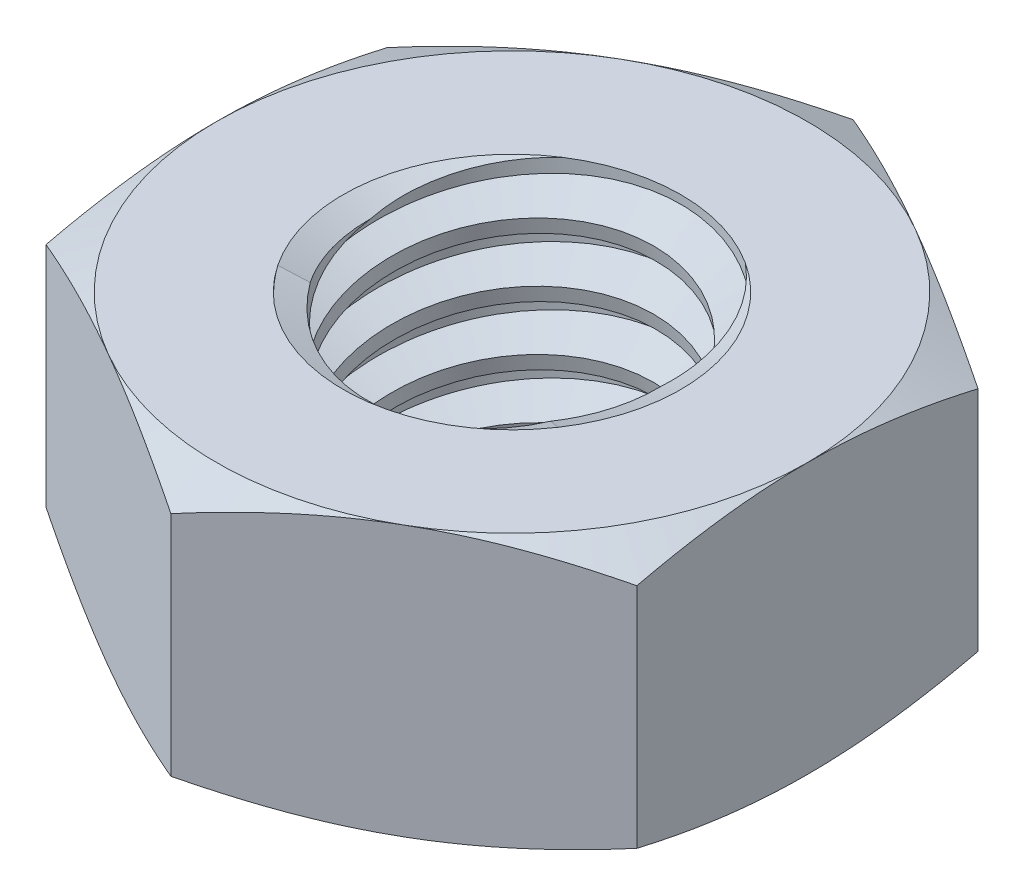
SolidWorks part; units mm, degrees
ref_plane "Front" through (0, 0, 0) normal (0, 0, 1) x (1, 0, 0)
ref_plane "Top" through (0, 0, 0) normal (0, 1, 0) x (1, 0, 0)
ref_plane "Right" through (0, 0, 0) normal (1, 0, 0) x (0, 0, -1)
sketch "Sketch1" plane through (0, 0, 0) normal (0, 1, 0) x (1, 0, 0)
  line L1 (0, 4.0415) -> (-3.5, 2.0207)
  line L2 (-3.5, 2.0207) -> (-3.5, -2.0207)
  line L3 (-3.5, -2.0207) -> (0, -4.0415)
  line L4 (0, -4.0415) -> (3.5, -2.0207)
  line L5 (3.5, -2.0207) -> (3.5, 2.0207)
  line L6 (3.5, 2.0207) -> (0, 4.0415)
  circle A0 centre (0, 0) radius 3.5 construction
  dimension "Hex Flats" = 7
extrude "Extrude1" add sketch "Sketch1" along normal mid plane 3.2
sketch "Sketch2" plane through (0, 0, 0) normal (1, 0, 0) x (0, 0, -1)
  line L0 (-2, -1.6) -> (-2, 1.6) construction
  line L1 (0, -1.6) -> (2, -1.6)
  line L2 (0, -1.6) -> (0, 1.6)
  line L3 (0, 1.6) -> (2, 1.6)
  line L4 (2, -1.6) -> (2, 1.6)
  line L5 (-2.0207, 1.6) -> (2.0207, 1.6) construction
  line L6 (-2.0207, -1.6) -> (2.0207, -1.6) construction
  line L7 (0, -3.6) -> (0, -1.6) construction
  dimension "Thread Dia" = 4
revolve "Revolve1" add sketch "Sketch2" angle 360 about L7
sketch "Sketch3" plane through (0, 0, 0) normal (1, 0, 0) x (0, 0, -1)
  line L0 (2, 1.6) -> (-2, 1.6) construction
  line L1 (-2, 1.6) -> (-2, 0.9) construction
  line L2 (-2, 0.9) -> (2, 1.6) construction
  line L3 (2, 1.6) -> (2.0151, 1.5138) construction
  line L4 (2.0151, 1.5138) -> (2.1207, 0.9105)
  line L5 (2.1207, 0.9105) -> (1.7097, 1.0606)
  line L6 (1.7097, 1.0606) -> (1.6796, 1.233)
  line L7 (1.6796, 1.233) -> (2.0151, 1.5138)
  line L8 (1.6947, 1.1468) -> (2.0679, 1.2121) construction
  line L9 (2, 1.6) -> (2, 1.2003) construction
  line L10 (2, 1.2003) -> (-2, 0.5003) construction
  line L11 (-2, 0.5003) -> (-2, 0.9) construction
  line L12 (-0.1312, 1.6) -> (0.1312, 0.1005) construction
  line L13 (-2, -1.6) -> (-2, 1.6) construction
  line L14 (0, 1.6) -> (2, 1.6) construction
  line L15 (2, -1.6) -> (2, 1.6) construction
  line L16 (0, 0) -> (0, 1.6) construction
  line L17 (-2.0151, 1.5138) -> (-2.1207, 0.9105) construction
  line L18 (-1.6796, 1.233) -> (-2.0151, 1.5138) construction
  line L19 (-1.7097, 1.0606) -> (-1.6796, 1.233) construction
  line L20 (-2.1207, 0.9105) -> (-1.7097, 1.0606) construction
  line L21 (0.1312, 1.6) -> (-0.1312, 0.1005) construction
  point P13 (0, 0.8503)
  dimension "D1" = 0.0875
  dimension "D2" = 0.175
  dimension "Thread Pitch" = 0.7
  dimension "D4" = 60
  dimension "D5" = 0.7
revolve "Cut-Revolve1" cut sketch "Sketch3" angle 360 about L12
pattern_linear "LPattern1" count 5 spacing 0.7 along (0, -1, 0) count 2 spacing 0.7 along (0, 1, 0) of "Cut-Revolve1"
sketch "Sketch4" plane through (0, 0, 0) normal (1, 0, 0) x (0, 0, -1)
  line L0 (0, 1.6) -> (2, 1.6)
  line L1 (2, 1.6) -> (1.6796, 1.4506)
  line L2 (1.6796, 1.4506) -> (1.6796, -1.4506)
  line L3 (1.6796, -1.4506) -> (2, -1.6)
  line L4 (2, -1.6) -> (0, -1.6)
  line L5 (0, -1.6) -> (0, 1.6)
  line L6 (2, -1.6) -> (2, 1.6) construction
  line L7 (0, 1.6) -> (2, 1.6) construction
  line L8 (0, -1.6) -> (2, -1.6) construction
  line L9 (0, -1.6) -> (0, 1.6) construction
  line L10 (0, 1.6) -> (0, 1.9535) construction
  dimension "D1" = 25
revolve "Cut-Revolve2" cut sketch "Sketch4" angle 360 about L10
combine bodies "Combine1" operation type subtract main body 112 bodies to subtract 111
sketch "Sketch5" plane through (0, 0, 0) normal (1, 0, 0) x (0, 0, -1)
  line L0 (0, -1.6) -> (3.5, -1.6)
  line L1 (3.5, -1.6) -> (4.0415, -1.3475)
  line L2 (4.0415, -1.3475) -> (4.0415, 1.3475)
  line L3 (4.0415, 1.3475) -> (3.5, 1.6)
  line L4 (0, 1.6) -> (0, 2.87)
  line L5 (0, 2.87) -> (5.3115, 2.87)
  line L6 (5.3115, 2.87) -> (5.3115, -2.87)
  line L7 (5.3115, -2.87) -> (0, -2.87)
  line L8 (0, -2.87) -> (0, -1.6)
  line L9 (3.5, 1.6) -> (3.5, -1.6) construction
  line L11 (0, -1.6) -> (2, -1.6) construction
  line L12 (3.5, 1.6) -> (0, 1.6)
  line L13 (4.0415, 0) -> (5.3115, 0) construction
  line L14 (4.0415, 1.6) -> (4.0415, -1.6) construction
  line L15 (0, -1.6) -> (0, 1.6) construction
  line L17 (0, 0) -> (3.5, 0) construction
  line L22 (0, 1.6) -> (2, 1.6) construction
  dimension "D1" = 25
  dimension "D2" = 1.27
  dimension "D3" = 3.2
revolve "Cut-Revolve3" cut sketch "Sketch5" angle 360 about L15
equation "\"D1@Sketch3\"=\"Thread Pitch@Sketch3\"/8"
equation "\"D2@Sketch3\"=\"Thread Pitch@Sketch3\"/4"
equation "\"D5@Sketch3\"=\"Thread Pitch@Sketch3\""
equation "\"D4@LPattern1\"=\"Thread Pitch@Sketch3\""
equation "\"D3@LPattern1\"=\"Thread Pitch@Sketch3\""
equation "\"D1@LPattern1\"=\"Height@Extrude1\"/\"Thread Pitch@Sketch3\""
